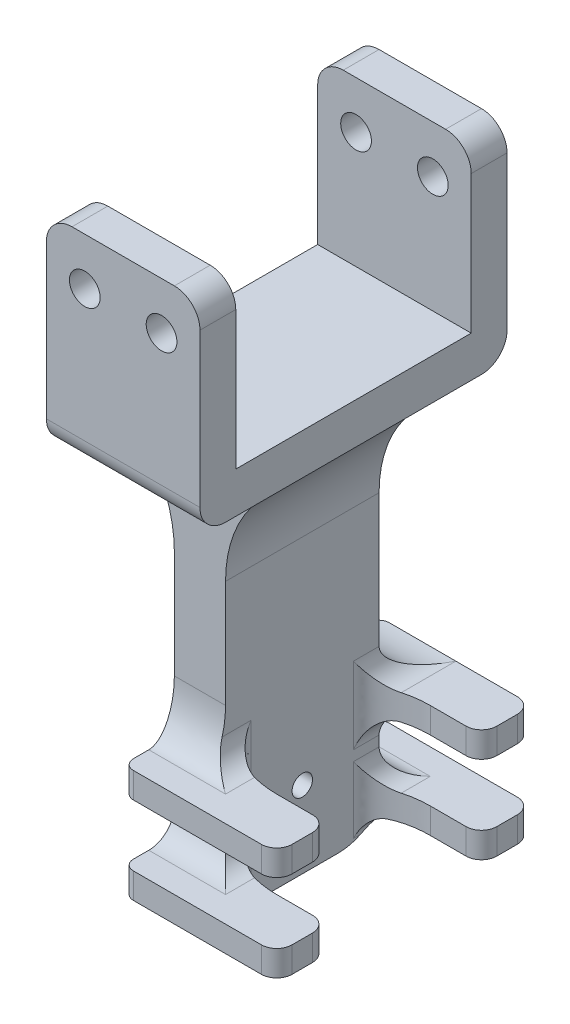
SolidWorks part; units mm, degrees
ref_plane "前视基准面" through (0, 0, 0) normal (0, 0, 1) x (1, 0, 0)
ref_plane "上视基准面" through (0, 0, 0) normal (0, 1, 0) x (1, 0, 0)
ref_plane "右视基准面" through (0, 0, 0) normal (1, 0, 0) x (0, 0, -1)
other "Configuration Table"
sketch "草图1" plane through (0, 0, 0) normal (1, 0, 0) x (0, 0, -1)
  line L1 (0, 0) -> (30, 0)
  line L2 (0, 0) -> (0, 75)
  line L3 (0, 75) -> (30, 75)
  line L4 (30, 0) -> (30, 75)
  dimension "D1" = 75
  dimension "D2" = 30
extrude "凸台-拉伸1" add sketch "草图1" along normal blind 10
sketch "草图2" plane through (0, 0, 0) normal (-1, 0, 0) x (0, 0, 1)
  line L0 (-15, 75) -> (-15, 0) construction
  line L1 (-30, 75) -> (0, 75) construction
  line L2 (0, 0) -> (-30, 0) construction
  circle A0 centre (-15, 15) radius 2
  point P9 (-15, 15)
  dimension "D1" = 4
  dimension "D2" = 15
extrude "切除-拉伸1" cut sketch "草图2" against normal up to next
sketch "草图6" plane through (10, 0, 0) normal (1, 0, 0) x (0, 0, -1)
  line L1 (0, 75) -> (30, 75)
  line L2 (0, 75) -> (0, 85)
  line L3 (0, 85) -> (30, 85)
  line L4 (30, 75) -> (30, 85)
  dimension "D1" = 10
extrude "凸台-拉伸3" add sketch "草图6" against normal up to surface (10 mm away) up to face at (0, 15, -13)
sketch "草图9" plane through (0, 0, 0) normal (0, 0, 1) x (1, 0, 0)
  line L0 (0, 15) -> (14.3297, 15) construction
  line L1 (0, 85) -> (0, 0) construction
  line L2 (10, 0) -> (0, 0) construction
  line L8 (0, 26) -> (30, 26)
  line L13 (0, 26) -> (0, 21)
  line L14 (0, 21) -> (30, 21)
  line L15 (30, 26) -> (30, 21)
  line L16 (0, 9) -> (30, 9)
  line L17 (0, 9) -> (0, 4)
  line L18 (0, 4) -> (30, 4)
  line L19 (30, 9) -> (30, 4)
  dimension "D1" = 15
  dimension "D2" = 12
  dimension "D3" = 5
  dimension "D4" = 5
  dimension "D5" = 6
  dimension "D6" = 30
ref_plane "基准面2" through (0, 0, -15) normal (0, 0, -1) x (-1, 0, 0)
extrude "凸台-拉伸5" add sketch "草图9" along normal blind 10
mirror "镜向7" about plane through (0, 0, -15) normal (0, 0, -1) of "凸台-拉伸5"
fillet "圆角5" radius 10 2 edges at (5, 0, -30) (5, 0, 0)
fillet "圆角6" radius 10 2 edges at (5, 4, -30) (5, 4, 0)
fillet "圆角7" radius 5 4 edges at (5, 9, -30) (5, 21, -30) (5, 21, 0) (5, 9, 0)
fillet "圆角8" radius 2 4 edges at (0, 23.5, 10) (0, 6.5, 10) (0, 23.5, -40) (0, 6.5, -40)
fillet "圆角10" radius 3 8 edges at (30, 6.5, -40) (30, 6.5, -30) (30, 23.5, -40) (30, 23.5, -30) (30, 23.5, 0) (30, 23.5, 10) (30, 6.5, 0) (30, 6.5, 10)
fillet "圆角11" radius 10 2 edges at (5, 26, 0) (5, 26, -30) second distance 5 first distance on face at (5, 55.5, 0) first distance on face at (15.8536, 26, -34.8018)
fillet "圆角12" radius 10 4 edges at (10, 23.5, 0) (10, 23.5, -30) (10, 6.5, -30) (10, 6.5, 0) second distance 5 first distance on face at (18.5, 23.5, 0) first distance on face at (18.5, 23.5, -30) first distance on face at (18.5, 6.5, -30) first distance on face at (18.5, 6.5, 0)
fillet "圆角13" radius 5 6 edges
fillet "圆角14" radius 3 2 edges
sketch "草图10" plane through (0, 0, 0) normal (-1, 0, 0) x (0, 0, 1)
  line L1 (-45, 85) -> (15, 85)
  line L2 (-45, 85) -> (-45, 77)
  line L3 (-45, 77) -> (15, 77)
  line L4 (15, 85) -> (15, 77)
  line L5 (0, 85) -> (0, 36) construction
  dimension "D1" = 8
  dimension "D2" = 60
  dimension "D3" = 15
extrude "凸台-拉伸6" add sketch "草图10" along normal blind 10 and the other way blind 20
sketch "草图15" plane through (0, 85, 0) normal (0, 1, 0) x (1, 0, 0)
  line L0 (20, -15) -> (20, 45) construction
  line L1 (-10, -15) -> (20, -15)
  line L2 (-10, -15) -> (-10, -8)
  line L3 (-10, -8) -> (20, -8)
  line L4 (20, -15) -> (20, -8)
  line L5 (20, -15) -> (-10, -15) construction
  point P7 (0, 0)
  point P10 (0, 0)
  dimension "D1" = 7
extrude "凸台-拉伸10" add sketch "草图15" along normal blind 32
mirror "镜向8" about plane through (0, 0, -15) normal (0, 0, -1) of "凸台-拉伸10"
fillet "圆角16" radius 25 2 edges at (10, 77, -15) (0, 77, -15)
sketch "草图18" plane through (0, 0, 0) normal (-1, 0, 0) x (0, 0, 1)
  circle A0 centre (-15, 15) radius 5.15
  dimension "D1" = 10.3
extrude "切除-拉伸3" cut sketch "草图18" against normal blind 2
sketch "草图19" plane through (0, 0, 15) normal (0, 0, 1) x (1, 0, 0)
  line L0 (5, 117) -> (5, 77) construction
  line L1 (-10, 117) -> (20, 117) construction
  line L2 (20, 77) -> (-10, 77) construction
  line L3 (20, 77) -> (-10, 77) construction
  circle A0 centre (-2.5, 107.75) radius 3
  circle A1 centre (12.5, 107.75) radius 3
  point P12 (0, 0)
  dimension "D2" = 6
  dimension "D3" = 6
  dimension "D1" = 30.75
  dimension "D4" = 15
  dimension "D5" = 7.5
extrude "切除-拉伸4" cut sketch "草图19" against normal blind 70
fillet "圆角17" radius 5 6 edges at (20, 117, -41.5) (20, 117, 11.5) (-10, 117, -41.5) (-10, 117, 11.5) (5, 77, -45) (5, 77, 15)
